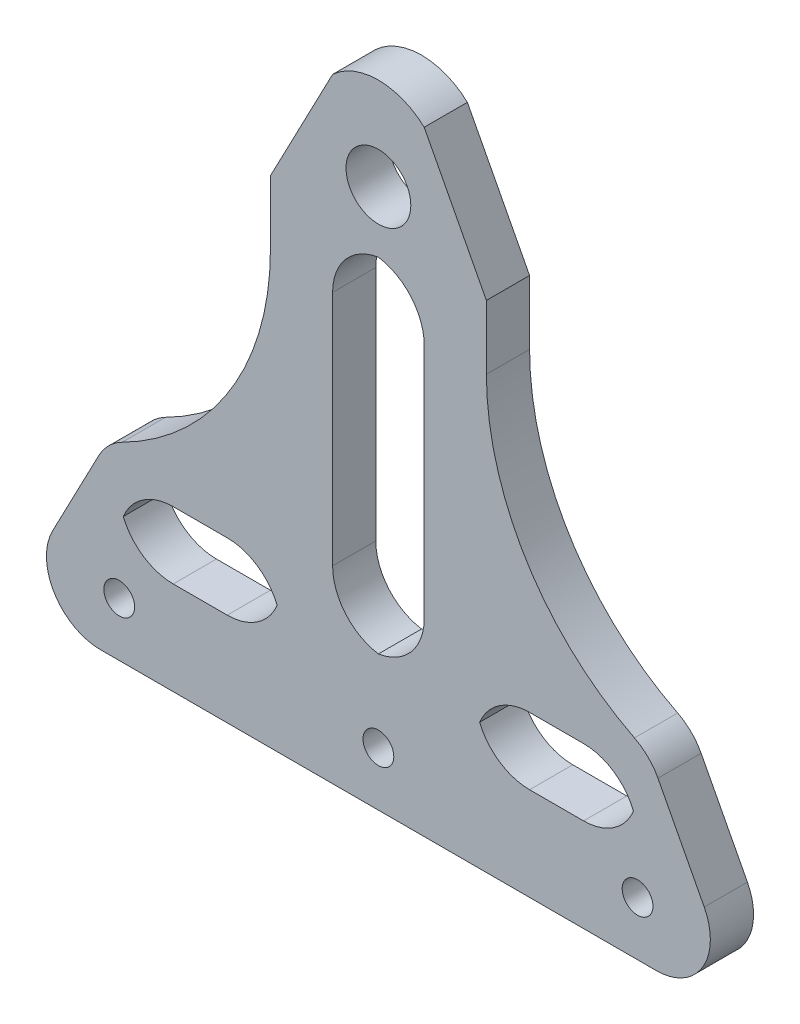
SolidWorks part; units mm, degrees
ref_plane "Front Plane" through (0, 0, 0) normal (0, 0, 1) x (1, 0, 0)
ref_plane "Top Plane" through (0, 0, 0) normal (0, 1, 0) x (1, 0, 0)
ref_plane "Right Plane" through (0, 0, 0) normal (1, 0, 0) x (0, 0, -1)
sketch "Sketch1" plane through (0, 0, 0) normal (0, 0, 1) x (1, 0, 0)
  line L0 (-34, -17) -> (0, 48)
  line L1 (-34, -17) -> (34, -17)
  line L2 (-34, -17) -> (-34, 17)
  line L3 (-34, 17) -> (34, 17)
  line L4 (34, -17) -> (34, 17)
  line L5 (-34, -17) -> (34, 17) construction
  line L6 (-34, 17) -> (34, -17) construction
  line L7 (0, 48) -> (34, -17)
  line L13 (34, 17) -> (11, 17)
  line L14 (34, 17) -> (34, 0)
  line L25 (34, 0) -> (10, 0)
  line L26 (34, 0) -> (34, 39.8919)
  line L27 (34, 39.8919) -> (10, 39.8919)
  line L28 (10, 0) -> (10, 39.8919)
  line L29 (-34, 0) -> (-10, 0)
  line L30 (-34, 0) -> (-34, 39.8919)
  line L31 (-34, 39.8919) -> (-10, 39.8919)
  line L32 (-10, 0) -> (-10, 39.8919)
  line L33 (-4.2411, 27.4049) -> (4.2411, 27.4049)
  line L34 (-4.2411, 27.4049) -> (-4.2411, -4.5265)
  line L35 (-4.2411, -4.5265) -> (4.2411, -4.5265)
  line L36 (4.2411, 27.4049) -> (4.2411, -4.5265)
  line L37 (-24, -2.159) -> (-9, -2.159)
  line L38 (-24, -2.159) -> (-24, -8.3593)
  line L39 (-24, -8.3593) -> (-9, -8.3593)
  line L40 (-9, -2.159) -> (-9, -8.3593)
  line L41 (24, -8.3593) -> (9, -8.3593)
  line L42 (24, -8.3593) -> (24, -2.159)
  line L43 (24, -2.159) -> (9, -2.159)
  line L44 (9, -8.3593) -> (9, -2.159)
  circle A0 centre (0, 33) radius 3
  circle A1 centre (0, -12) radius 1.425
  circle A2 centre (24, -12) radius 1.425
  circle A3 centre (-24, -12) radius 1.425
  arc A4 (-4.2411, 39.8919) -> (4.2411, 39.8919) centre (0, 35.3126) cw
  point P0 (0, 0)
  dimension "D9" = 6
  dimension "D14" = 2.85
  dimension "D15" = 2.85
  dimension "D16" = 2.85
  dimension "D1" = 68
  dimension "D2" = 50
  dimension "D3" = 15
  dimension "D4" = 10
  dimension "D5" = 10
  dimension "D6" = 0
  dimension "D7" = 5
  dimension "D8" = 0
  dimension "D10" = 24
  dimension "D11" = 24
  dimension "D12" = 15
  dimension "D13" = 15
  dimension "D17" = 0
extrude "Boss-Extrude1" add sketch "Sketch1" along normal blind 4 contours A4 L3 A0 | L0 L1 L7 L26 L3 A3 A2 A1 region at (0, 28.608, 0) region at (0, -6.2797, 0)
fillet "Fillet3" radius 25 2 edges at (10, 0, 2) (-10, 0, 2)
fillet "Fillet4" radius 5 16 edges at (34, -17, 2) (-34, -17, 2) (4.2411, -4.5265, 2) (-4.2411, -4.5265, 2) (4.2411, 27.4049, 2) (-4.2411, 27.4049, 2) (-24, -2.159, 2) (-24, -8.3593, 2) (-9, -8.3593, 2) (-9, -2.159, 2) (9, -8.3593, 2) (24, -8.3593, 2) (9, -2.159, 2) (24, -2.159, 2) (25.1077, 0, 2) (-25.1077, 0, 2)
